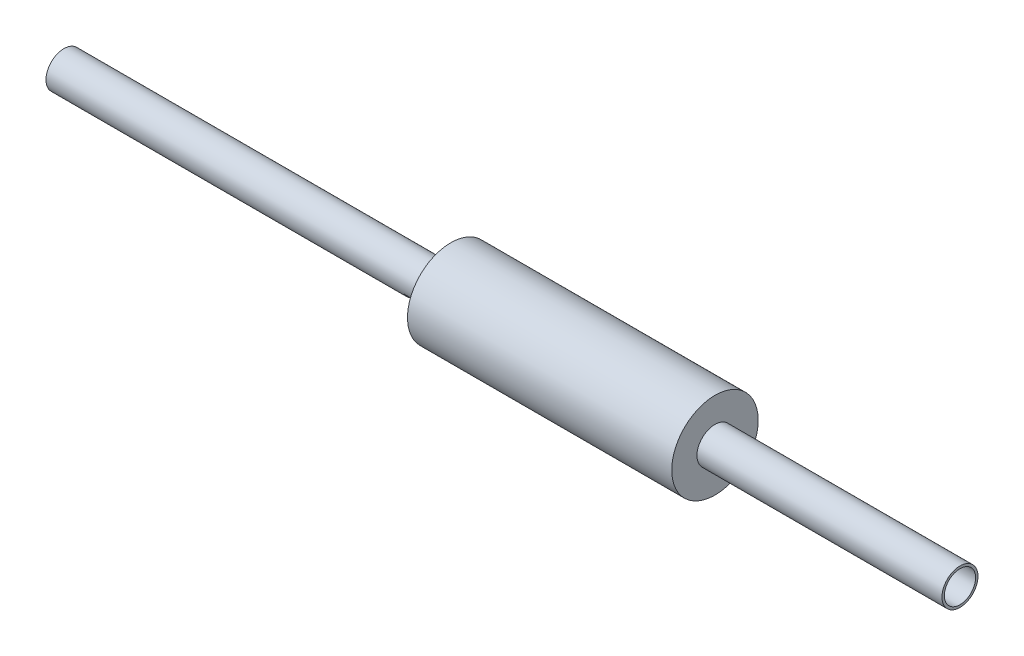
SolidWorks part; units mm, degrees
ref_plane "Front Plane" through (0, 0, 0) normal (0, 0, 1) x (1, 0, 0)
ref_plane "Top Plane" through (0, 0, 0) normal (0, 1, 0) x (1, 0, 0)
ref_plane "Right Plane" through (0, 0, 0) normal (1, 0, 0) x (0, 0, -1)
sketch "Sketch1" plane through (0, 0, 0) normal (0, 0, 1) x (1, 0, 0)
  line L0 (196.3562, 0) -> (-196.3562, 0) construction
  line L3 (157, 7.5) -> (-216, 7.5)
  line L4 (0, -42.6677) -> (0, 42.6677) construction
  line L7 (157, 7.5) -> (157, 0)
  line L8 (157, 0) -> (-157, 0) construction
  line L9 (-216, 7.5) -> (-216, 6.5)
  line L10 (-216, 6.5) -> (-157, 6.5)
  line L11 (-157, 6.5) -> (-157, 0) construction
  line L12 (-55, 18) -> (55, 18)
  line L13 (-55, 18) -> (-55, 7.5)
  line L14 (55, 18) -> (55, 7.5)
  line L15 (-157, 6.5) -> (157, 6.5)
  point P3 (0, 18)
  point P10 (0, 0)
  dimension "D1" = 157
  dimension "D3" = 59
  dimension "D4" = 15
  dimension "D5" = 13
  dimension "D6" = 36
  dimension "D7" = 110
  dimension "D2" = 157
revolve "Revolve1" add sketch "Sketch1" angle 360 about L0 region at (-29.5, 7, 0) region at (0, 12.75, 0)
sketch "Sketch2" plane through (0, 0, 0) normal (0, 1, 0) x (1, 0, 0)
  line L0 (157, 0) -> (-157, 0) construction
  line L1 (-68, -6.5) -> (-60, -6.5)
  line L2 (-68, -6.5) -> (-68, 6.5)
  line L3 (-68, 6.5) -> (-60, 6.5)
  line L4 (-60, -6.5) -> (-60, 6.5)
  line L5 (-68, -6.5) -> (-60, 6.5) construction
  line L6 (-68, 6.5) -> (-60, -6.5) construction
  point P0 (-64, 0)
  dimension "D1" = 5
  dimension "D2" = 8
  dimension "D3" = 13
extrude "Cut-Extrude1" cut sketch "Sketch2" against normal up to next
equation "\"D2@Sketch1\"=\"D1@Sketch1\""
